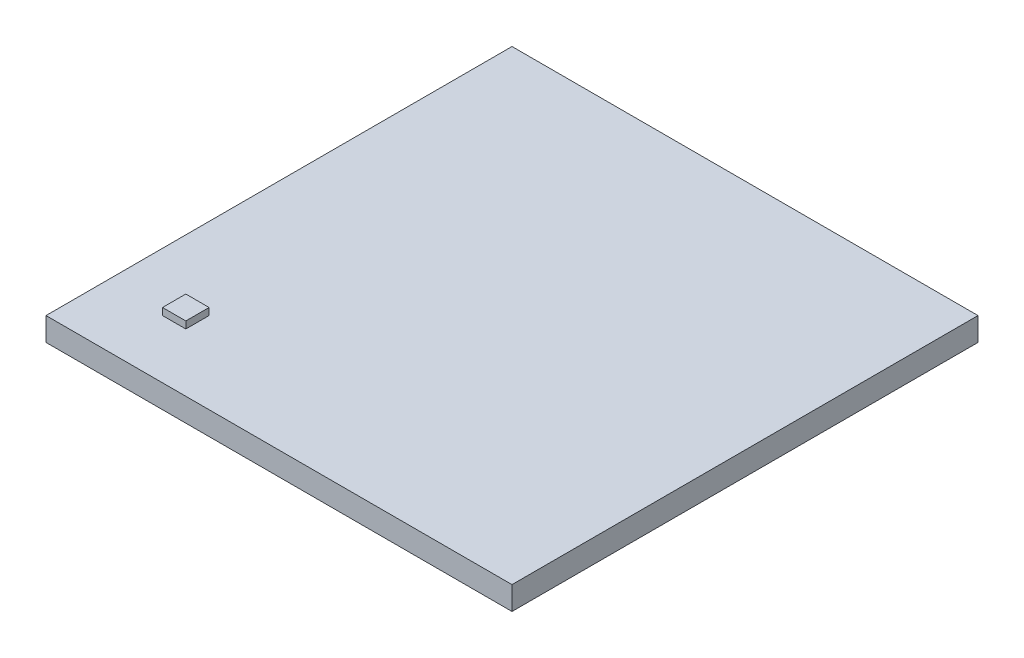
SolidWorks part; units mm, degrees
ref_plane "Plan de face" through (0, 0, 0) normal (0, 0, 1) x (1, 0, 0)
ref_plane "Plan de dessus" through (0, 0, 0) normal (0, 1, 0) x (1, 0, 0)
ref_plane "Plan de droite" through (0, 0, 0) normal (1, 0, 0) x (0, 0, -1)
sketch "Esquisse1" plane through (0, 0, 0) normal (0, 1, 0) x (1, 0, 0)
  line L0 (0, 0) -> (200, 0)
  line L1 (0, 0) -> (-200, 0)
  line L2 (-200, 0) -> (-200, 400)
  line L3 (-200, 400) -> (200, 400)
  line L4 (200, 400) -> (200, 0)
  line L5 (0, 0) -> (0, 50)
  line L6 (0, 50) -> (-150, 50)
  line L7 (-150, 50) -> (-150, 70)
  line L8 (-150, 70) -> (-130, 70)
  line L9 (-130, 70) -> (-130, 50)
extrude "Boss.-Extru.1" add sketch "Esquisse1" against normal blind 20 contours L4 L0 L1 L2 L3
extrude "Boss.-Extru.2" add sketch "Esquisse1<3>" along normal blind 6 contours L9 L8 L7 L6 region at (-140, 0, -60)
sketch "Esquisse1<3>" plane through (0, 0, 0) normal (0, 1, 0) x (1, 0, 0) same geometry as "Esquisse1"
sketch "Esquisse2" plane through (0, 0, 0) normal (0, 1, 0) x (1, 0, 0)
  line L0 (200, 400) -> (-200, 400)
  line L1 (-200, 400) -> (0, 400)
  line L2 (0, 0) -> (0, 400)
  line L3 (-200, 200) -> (200, 200)
  line L4 (-200, 0) -> (-200, 400) construction
  line L5 (200, 400) -> (200, 0) construction
